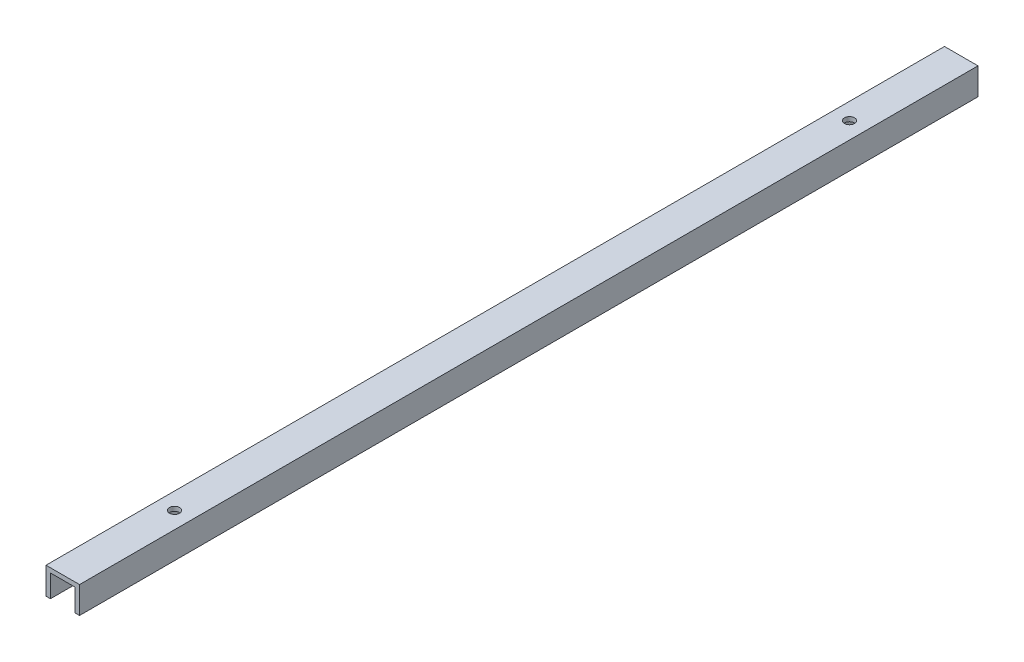
SolidWorks part; units mm, degrees
note: The reader was unsure of these and kept them because the rebuilt part matched: thickness of "Базовая кромка2", "Листовой металл2", "Листовой металл4".
material "1060 Сплав"
ref_plane "Front" through (0, 0, 0) normal (0, 0, 1) x (1, 0, 0)
ref_plane "Top" through (0, 0, 0) normal (0, 1, 0) x (1, 0, 0)
ref_plane "Right" through (0, 0, 0) normal (1, 0, 0) x (0, 0, -1)
sketch "Эскиз6" plane through (0, 0, 0) normal (0, 0, 1) x (1, 0, 0)
  line L0 (0, 0) -> (-2, 0)
  line L1 (-2, 0) -> (-2, 12)
  line L2 (-2, 12) -> (13, 12)
  line L3 (13, 12) -> (13, 0)
  line L4 (0, 10) -> (11, 10)
  line L5 (13, 0) -> (11, 0)
  line L6 (11, 0) -> (11, 10)
  line L7 (0, 10) -> (0, 0)
  dimension "D1" = 12
  dimension "D2" = 2
  dimension "D3" = 15
  dimension "D4" = 2
  dimension "D5" = 2
base flange "Базовая кромка2" sketch "Эскиз6" thickness 402 reverse thickness direction no parameters "D1"=0
sketch "Эскиз7" plane through (0, 12, 0) normal (0, 1, 0) x (1, 0, 0)
  line L0 (13, 0) -> (-2, 0) construction
  line L1 (-2, 402) -> (-2, 0) construction
  line L2 (0, 402) -> (11, 402) construction
  circle A0 centre (5.5, 50) radius 2.25
  circle A1 centre (5.5, 352) radius 2.25
  dimension "D2" = 7.5
  dimension "D3" = 4.5
  dimension "D4" = 50
  dimension "D5" = 4.5
  dimension "D6" = 7.5
  dimension "D1" = 50
extrude "Вырез-Вытянуть1" cut sketch "Эскиз7" against normal through all normal cut yes
sketch "Сгиб-Линии3" [suppressed] plane through (0, 0, 0) normal (0, 1, 0) x (1, 0, 0)
sketch "Граничная рамка3" [suppressed] plane through (0, 0, 0) normal (0, 1, 0) x (1, 0, 0)
sheet metal parameters "Листовой металл2" thickness 402 parameters "D1"=0
flat pattern "Развертка2" [suppressed]
sketch "Сгиб-Линии4" plane through (0, 0, 0) normal (0, 1, 0) x (1, 0, 0)
sketch3d "Граничная рамка4" [suppressed]
  line L0 (-2, 0, 0) -> (13, 0, 0) construction
  line L1 (-2, 10, 0) -> (13, 10, 0) construction
  line L2 (-2, 0, 0) -> (-2, 10, 0) construction
  line L3 (13, 0, 0) -> (13, 10, 0) construction
sheet metal parameters "Листовой металл4" thickness 402 parameters "D1"=0, "D7"=404
flat pattern "Развертка2"
sketch "Сгиб-Линии4" plane through (0, 0, 0) normal (0, 1, 0) x (1, 0, 0)
sketch3d "Граничная рамка4" [suppressed]
  line L0 (-2, 0, 0) -> (13, 0, 0) construction
  line L1 (-2, 12, 0) -> (13, 12, 0) construction
  line L2 (-2, 0, 0) -> (-2, 12, 0) construction
  line L3 (13, 0, 0) -> (13, 12, 0) construction
